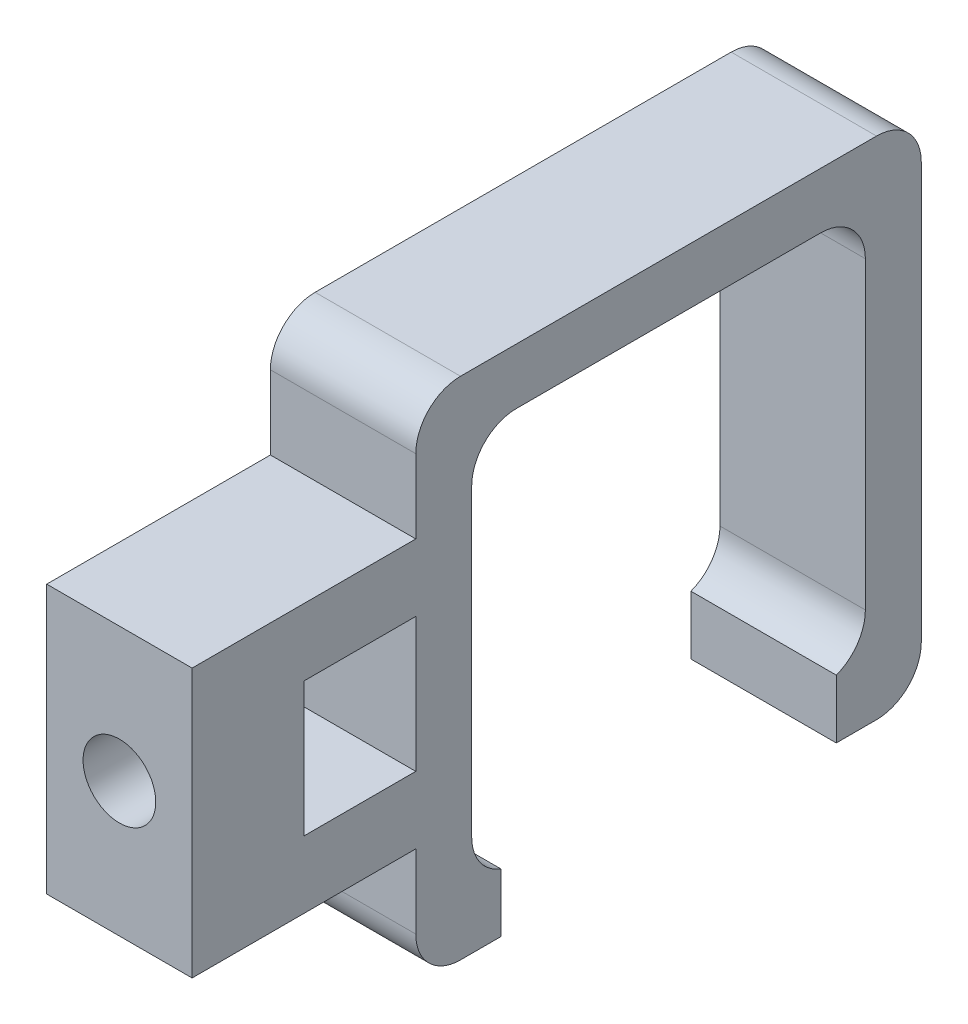
SolidWorks part; units mm, degrees
ref_plane "Front Plane" through (0, 0, 0) normal (0, 0, 1) x (1, 0, 0)
ref_plane "Top Plane" through (0, 0, 0) normal (0, 1, 0) x (1, 0, 0)
ref_plane "Right Plane" through (0, 0, 0) normal (1, 0, 0) x (0, 0, -1)
sketch "Sketch1" plane through (0, 0, 0) normal (1, 0, 0) x (0, 0, -1)
  line L1 (17.6, -17.6) -> (-17.6, -17.6)
  line L2 (17.6, -17.6) -> (17.6, 17.6)
  line L3 (17.6, 17.6) -> (-17.6, 17.6)
  line L4 (-17.6, -17.6) -> (-17.6, 17.6)
  line L5 (17.6, -17.6) -> (-17.6, 17.6) construction
  line L6 (17.6, 17.6) -> (-17.6, -17.6) construction
  line L7 (22.6, -22.6) -> (-22.6, -22.6)
  line L8 (22.6, -22.6) -> (22.6, 22.6)
  line L9 (22.6, 22.6) -> (-22.6, 22.6)
  line L10 (-22.6, -22.6) -> (-22.6, 22.6)
  line L11 (22.6, -22.6) -> (-22.6, 22.6) construction
  line L12 (22.6, 22.6) -> (-22.6, -22.6) construction
  point P0 (0, 0)
  point P6 (0, 0)
  dimension "D1" = 35.2
  dimension "D2" = 35.2
  dimension "D3" = 5
  dimension "D4" = 5
extrude "Boss-Extrude1" add sketch "Sketch1" against normal blind 13
fillet "Fillet1" radius 4 8 edges at (-6.5, -22.6, -22.6) (-6.5, -22.6, 22.6) (-6.5, 22.6, 22.6) (-6.5, 22.6, -22.6) (-6.5, -17.6, -17.6) (-6.5, 17.6, -17.6) (-6.5, -17.6, 17.6) (-6.5, 17.6, 17.6)
sketch "Sketch3" plane through (0, 0, 0) normal (1, 0, 0) x (0, 0, -1)
  line L0 (-15, -17.347) -> (-15, -22.6)
  line L2 (-18.6, -22.6) -> (18.6, -22.6) construction
  line L3 (-15, -22.6) -> (15, -22.6)
  line L4 (15, -22.6) -> (15, -17.347)
  line L5 (15, -17.347) -> (-15, -17.347)
  arc A2 (13.6, -17.6) -> (17.6, -13.6) centre (13.6, -13.6) ccw construction
  point P2 (0, 0)
  point P6 (0, -22.6)
  point P9 (0, 0)
  dimension "D1" = 30
extrude "Cut-Extrude1" cut sketch "Sketch3" against normal through all
sketch "Sketch4" plane through (0, 0, 22.6) normal (0, 0, 1) x (1, 0, 0)
  line L0 (0, 0) -> (-13, 0) construction
  line L1 (0, 18.6) -> (0, -18.6) construction
  line L2 (-13, 18.6) -> (-13, -18.6) construction
  line L3 (-13, -6) -> (-13, -12)
  line L4 (-13, 6) -> (0, 6)
  line L5 (-13, 6) -> (-13, 12)
  line L6 (-13, 12) -> (0, 12)
  line L7 (0, 6) -> (0, 12)
  line L8 (0, -6) -> (0, -12)
  line L9 (-13, -6) -> (0, -6)
  line L10 (-13, -12) -> (0, -12)
  dimension "D1" = 6
  dimension "D2" = 12
extrude "Boss-Extrude2" add sketch "Sketch4" along normal blind 10
sketch "Sketch5" plane through (0, 0, 32.6) normal (0, 0, 1) x (1, 0, 0)
  line L1 (-13, 12) -> (0, 12)
  line L2 (-13, 12) -> (-13, -12)
  line L3 (-13, -12) -> (0, -12)
  line L4 (0, 12) -> (0, -12)
  circle A0 centre (-6.5, 0) radius 3.25
  point P8 (-6.5, 12)
  point P9 (0, 0)
  dimension "D1" = 6.5
extrude "Boss-Extrude3" add sketch "Sketch5" along normal blind 10
